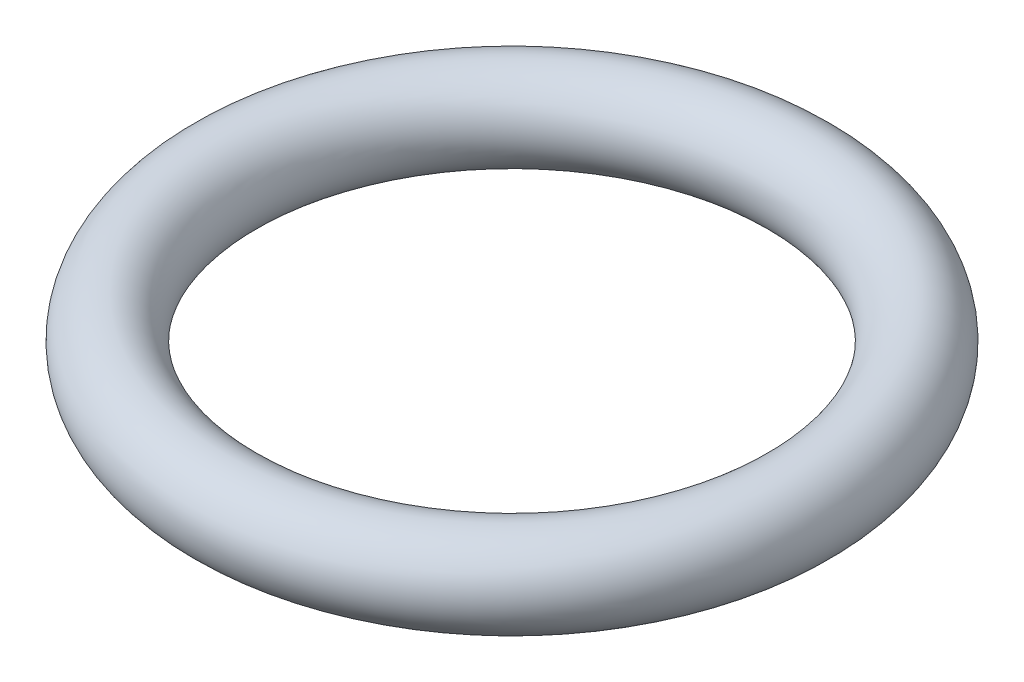
SolidWorks part; units mm, degrees
ref_plane "Front Plane" through (0, 0, 0) normal (0, 0, 1) x (1, 0, 0)
ref_plane "Top Plane" through (0, 0, 0) normal (0, 1, 0) x (1, 0, 0)
ref_plane "Right Plane" through (0, 0, 0) normal (1, 0, 0) x (0, 0, -1)
sketch "Sketch1" plane through (0, 0, 0) normal (0, 1, 0) x (1, 0, 0)
  circle A0 centre (0, 0) radius 4.125
  dimension "D1" = 8.25
sketch "Sketch2" plane through (0, 0, 0) normal (1, 0, 0) x (0, 0, -1)
  line L0 (4.125, 0) -> (-4.125, 0) construction
  circle A0 centre (-4.125, 0) radius 0.625
  dimension "D1" = 1.25
sweep "Sweep1" add profiles "Sketch2" path "Sketch1"
